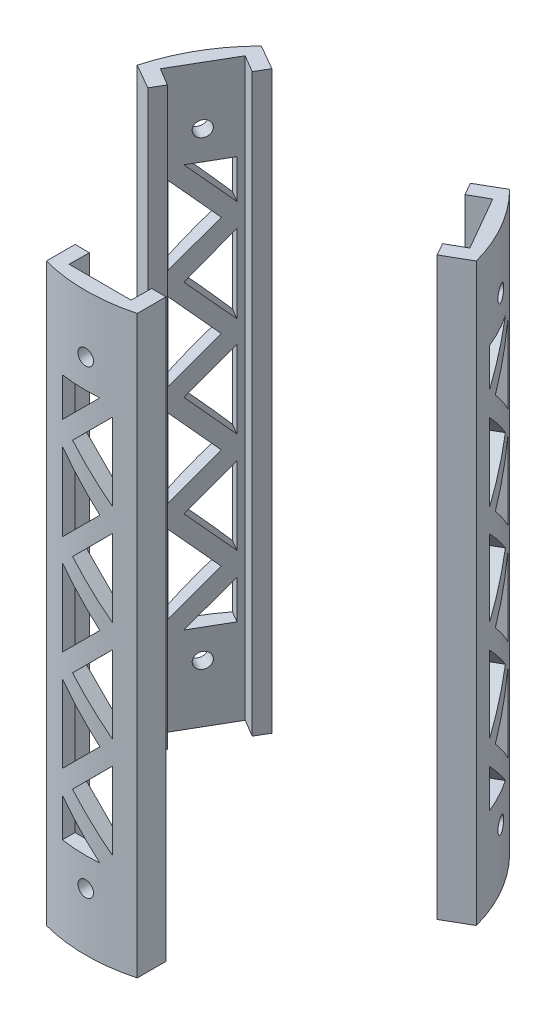
SolidWorks part; units mm, degrees
material "ABS"
ref_plane "Front Plane" through (0, 0, 0) normal (0, 0, 1) x (1, 0, 0)
ref_plane "Top Plane" through (0, 0, 0) normal (0, 1, 0) x (1, 0, 0)
ref_plane "Right Plane" through (0, 0, 0) normal (1, 0, 0) x (0, 0, -1)
sketch "Sketch1" plane through (0, 0, 0) normal (0, 1, 0) x (1, 0, 0)
  line L0 (0, 0) -> (0, -30.5) construction
  line L1 (0, 0) -> (26.4138, 15.25) construction
  line L2 (0, 0) -> (-26.4138, 15.25) construction
  line L3 (0, 0) -> (29.4607, 7.894) construction
  line L4 (0, 0) -> (21.5668, 21.5668) construction
  line L5 (21.5668, 21.5668) -> (29.4607, 7.894) construction
  line L6 (21.5668, 21.5668) -> (17.2366, 19.0668)
  line L7 (29.4607, 7.894) -> (25.1306, 5.394)
  line L8 (17.2366, 19.0668) -> (18.4866, 16.9017)
  line L9 (25.1306, 5.394) -> (23.9083, 7.5748)
  line L10 (18.4866, 16.9017) -> (21.5668, 18.6313)
  line L11 (23.9083, 7.5748) -> (26.9475, 9.2782)
  line L12 (21.5668, 18.6313) -> (26.9475, 9.2782)
  line L13 (-5.3942, -24.4926) -> (-5.4386, -27.9763)
  line L14 (-7.894, -24.4607) -> (-5.3942, -24.4926)
  line L15 (-7.894, -29.4607) -> (-7.894, -24.4607)
  line L16 (5.394, -24.4607) -> (5.3518, -27.993)
  line L17 (5.3518, -27.993) -> (-5.4386, -27.9763)
  line L18 (7.894, -24.4607) -> (5.394, -24.4607)
  line L19 (7.894, -29.4607) -> (7.894, -24.4607)
  line L20 (-18.5141, 16.9178) -> (-21.5089, 18.6981)
  line L21 (-17.2366, 19.0668) -> (-18.5141, 16.9178)
  line L22 (-21.5668, 21.5668) -> (-17.2366, 19.0668)
  line L23 (-23.8806, 7.559) -> (-26.9185, 9.3617)
  line L24 (-26.9185, 9.3617) -> (-21.5089, 18.6981)
  line L25 (-25.1306, 5.394) -> (-23.8806, 7.559)
  line L26 (-29.4607, 7.894) -> (-25.1306, 5.394)
  circle A0 centre (0, 0) radius 30.5
  circle A1 centre (0, 0) radius 28.5
  point P4 (20.1525, 20.1525)
  point P10 (27.5289, 7.3763)
  point P35 (0, 0)
  dimension "D1" = 61
  dimension "D2" = 57
  dimension "D3" = 120
  dimension "D4" = 120
  dimension "D5" = 15
  dimension "D6" = 15
  dimension "D7" = 5
  dimension "D8" = 90
  dimension "D9" = 5
  dimension "D10" = 90
  dimension "D11" = 2.5
  dimension "D12" = 2.5
  dimension "D13" = 3
extrude "Boss-Extrude1" add sketch "Sketch1" along normal blind 100 contours A1 L15 A0 L19 | L15 A1 L13 L14 | L16 A1 L19 L18 | L17 A1 region at (0, 0, 29.1401) region at (6.5943, 0, 26.094) region at (-6.6191, 0, 26.0884) region at (-0.0437, 0, 28.1909)
sketch "Sketch2" plane through (-0.0434, 0, 27.9846) normal (0.0016, 0, -1) x (-1, 0, -0.0016)
  line L0 (-5.3952, 100) -> (5.3952, 100) construction
  line L1 (-5.3952, 0) -> (5.3952, 0) construction
  circle A0 centre (0, 90) radius 1.35
  circle A1 centre (0, 10) radius 1.35
  dimension "D1" = 2.7
  dimension "D2" = 10
  dimension "D3" = 2.7
  dimension "D4" = 10
extrude "Cut-Extrude1" cut sketch "Sketch2" against normal blind 100
sketch "Sketch3" plane through (-0.0434, 0, 27.9846) normal (0.0016, 0, -1) x (-1, 0, -0.0016)
  line L0 (-5.3952, 100) -> (-5.3952, 0) construction
  line L1 (-4.3952, 85) -> (4.3562, 85)
  line L2 (-4.3952, 85) -> (-4.3952, 15)
  line L3 (-4.3952, 15) -> (4.3562, 15)
  line L4 (4.3562, 85) -> (4.3562, 15)
  line L5 (5.3562, 100) -> (5.3562, 0) construction
  line L6 (-4.3952, 85) -> (4.3562, 76.2486)
  line L7 (4.3562, 76.2486) -> (-4.3952, 67.4972)
  line L8 (-4.3952, 67.4972) -> (4.3562, 58.7458)
  line L9 (4.3562, 58.7458) -> (-4.3952, 50)
  line L10 (-4.3952, 50) -> (4.3562, 41.243)
  line L11 (4.3562, 41.243) -> (-4.3952, 32.4972)
  line L12 (-4.3952, 32.4972) -> (4.3562, 23.7402)
  line L13 (4.3562, 23.7402) -> (-4.3952, 15)
  line L14 (-2.3952, 85) -> (4.3562, 78.2486)
  line L15 (-4.3952, 83) -> (2.3562, 76.2486)
  line L16 (2.3562, 76.2486) -> (-4.3952, 69.4972)
  line L17 (-4.3952, 65.4972) -> (2.3562, 58.7458)
  line L18 (-4.3952, 48) -> (2.3562, 41.243)
  line L19 (-4.3952, 30.4972) -> (2.3562, 23.7402)
  line L20 (2.3562, 58.7458) -> (-4.3952, 51.9944)
  line L21 (2.3562, 41.243) -> (-4.3952, 34.4916)
  line L22 (2.3562, 23.7402) -> (-4.3952, 16.9888)
  line L23 (4.3562, 74.2486) -> (-2.3952, 67.3478)
  line L24 (4.3562, 56.7458) -> (-2.3952, 50)
  line L25 (4.3562, 39.243) -> (-2.3952, 32.4972)
  line L26 (-2.3952, 67.3478) -> (4.3562, 60.5964)
  line L27 (-2.3952, 50) -> (4.3562, 43.2486)
  line L28 (-2.3952, 32.4972) -> (4.3562, 25.7458)
  line L29 (4.3562, 21.7402) -> (-2.3952, 15)
  circle A0 centre (0, 90) radius 1.35 construction
  circle A1 centre (0, 10) radius 1.35 construction
  dimension "D1" = 1
  dimension "D2" = 1
  dimension "D3" = 5
  dimension "D4" = 5
  dimension "D5" = 2
  dimension "D6" = 2
  dimension "D7" = 2
  dimension "D8" = 2
  dimension "D9" = 2
  dimension "D10" = 2
  dimension "D11" = 2
  dimension "D12" = 2
  dimension "D13" = 2
  dimension "D14" = 2
  dimension "D15" = 2
  dimension "D16" = 2
extrude "Cut-Extrude5" cut sketch "Sketch3" against normal blind 100 contours L16 L15 L2 | L23 L26 L4 | L20 L17 L2 | L24 L27 L4 | L21 L18 L2 | L25 L28 L4 | L22 L19 L2 | L1 L14 L4 | L4 L29 L3 region at (-2.1491, 82.7495, 27.9814) region at (2.1013, 76.2486, 27.988) region at (-2.1491, 67.3976, 27.9814) region at (2.1013, 58.7458, 27.988) region at (-2.1491, 49.9981, 27.9814) region at (2.1013, 41.2449, 27.988) region at (-2.1491, 32.4954, 27.9814) region at (2.1013, 23.7421, 27.988) region at (-2.1491, 17.2467, 27.9814)
sketch "Sketch5" plane through (0, 0, 0) normal (0, 1, 0) x (1, 0, 0)
  line L0 (0, 0) -> (0, 32.3542) construction
ref_axis "Axis1" through (0, -5, 0) along (0, 1, 0)
pattern_circular "CirPattern3" count 3 every 120 about axis through (0, -5, 0) along (0, 1, 0) of bodies 105
